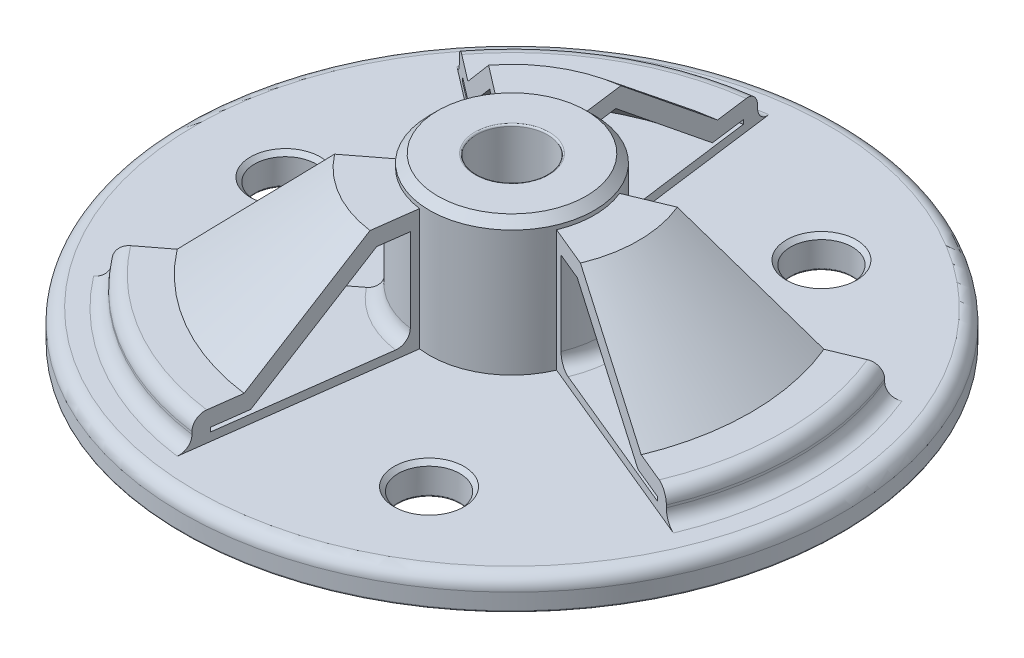
SolidWorks part; units mm, degrees
note: '?' marks a value the reader was unsure of.
material "ABS"
ref_plane "Front Plane" through (0, 0, 0) normal (0, 0, 1) x (1, 0, 0)
ref_plane "Top Plane" through (0, 0, 0) normal (0, 1, 0) x (1, 0, 0)
ref_plane "Right Plane" through (0, 0, 0) normal (1, 0, 0) x (0, 0, -1)
sketch "Sketch1" plane through (0, 0, 0) normal (0, 0, 1) x (1, 0, 0)
  line L0 (0, 0) -> (0, 25.4) construction
  line L1 (5.461, 25.4) -> (12.7, 25.4)
  line L2 (5.461, 0) -> (50.8, 0)
  line L3 (50.8, 0) -> (50.8, 4.7625)
  line L4 (50.8, 4.7625) -> (12.7, 4.7625)
  line L5 (12.7, 4.7625) -> (12.7, 25.4)
  line L6 (5.461, 25.4) -> (5.461, 0)
  dimension "D1" = 5.461
  dimension "D2" = 12.7
  dimension "D3" = 50.8
  dimension "D4" = 4.7625
  dimension "D5" = 25.4
revolve "Revolve1" add sketch "Sketch1" angle 360 about L0
hole_wizard "CBORE for #10 Socket Head Cap Screw1" positions "Sketch4" profile "Sketch6" counterbore size "#10" standard "ANSI Inch" end condition through all
sketch "Sketch4" plane through (0, 4.7625, 0) normal (0, 1, 0) x (1, 0, 0)
  line L4 (0, 0) -> (-34.925, 0) construction
  line L6 (0, 0) -> (17.4625, 30.2459) construction
  line L7 (0, 0) -> (17.4625, -30.2459) construction
  circle A1 centre (0, 0) radius 34.925 construction
  point P40 (-34.925, 0)
  point P43 (17.4625, -30.2459)
  point P46 (17.4625, 30.2459)
  dimension "D1" = 69.85
sketch "Sketch6" plane through (17.4625, 4.7625, -30.2459) normal (1, 0, 0) x (0, 0, 1)
  line L0 (0, 0) -> (0, 4.7625)
  line L1 (0, 4.7625) -> (2.8067, 4.7625)
  line L3 (2.8067, 4.7625) -> (2.8067, 4.826)
  line L4 (4.7625, 4.826) -> (2.8067, 4.826)
  line L5 (4.7625, 4.826) -> (4.7625, 0.635)
  line L6 (4.7625, 0.635) -> (5.3975, 0)
  line L7 (5.3975, 0) -> (0, 0)
  line L8 (-4.7625, 0.635) -> (-5.3975, 0) construction
  line L11 (0, -6.35) -> (0, 107.95) construction
  dimension "Thru Hole Dia." = 5.6134
  dimension "Thru Hole Depth" = 4.7625
  dimension "C'Bore Dia." = 9.525
  dimension "C'Bore Depth" = 4.826
  dimension "Near C'Sink Dia." = 10.795
  dimension "Near C'Sink Angle" = 90
sketch "Sketch7" plane through (0, 0, 0) normal (0, 0, 1) x (1, 0, 0)
  line L0 (12.7, 22.225) -> (19.05, 22.225)
  line L1 (12.7, 4.7625) -> (12.7, 25.4) construction
  line L2 (19.05, 22.225) -> (36.3504, 7.9375)
  line L3 (36.3504, 7.9375) -> (42.7004, 7.9375)
  line L4 (42.7004, 7.9375) -> (42.7004, 4.7625)
  line L5 (50.8, 4.7625) -> (-50.8, 4.7625) construction
  line L6 (12.7, 22.225) -> (12.7, 4.7625)
  line L7 (12.7, 4.7625) -> (42.7004, 4.7625)
  line L8 (0, 25.4) -> (0, 4.7625) construction
  line L9 (12.7, 25.4) -> (-12.7, 25.4) construction
  line L10 (12.7, 4.7625) -> (-12.7, 4.7625) construction
  dimension "D1" = 19.05
  dimension "D2" = 36.3504
  dimension "D3" = 3.175
  dimension "D4" = 6.35
  dimension "D5" = 3.175
revolve "Revolve-Thin1" add sketch "Sketch7" angle 45 mid plane about L8
ref_axis "Axis1" through (0, 25.4, 0) along (0, -1, 0)?
pattern_circular "CirPattern1" count 3 over 360 about axis through (0, 0, 0) along (0, 1, 0) of "Revolve-Thin1"
sketch "Sketch8" plane through (0, 0, 0) normal (0, -1, 0) x (1, 0, 0)
  circle A0 centre (0, 0) radius 7.9375
  circle A1 centre (0, 0) radius 5.461
  dimension "D1" = 15.875
extrude "Boss-Extrude1" add sketch "Sketch8" along normal blind 12.7 draft 1
fillet "Fillet1" radius 2.032 10 edges at (-21.9852, 4.7625, -38.0795) (-21.9852, 9.2075, -38.0795) (-6.985, 6.0325, -12.0984) (43.9704, 4.7625, 0) (43.9704, 9.2075, 0) (13.97, 6.0325, 0) (0, 4.7625, -50.8) (-21.9852, 4.7625, 38.0795) (-21.9852, 9.2075, 38.0795) (-6.985, 6.0325, 12.0984)
fillet "Fillet2" radius 0.254 8 edges at (0, 25.4, -5.461) (0, 0, -50.8) (-34.925, 0, -4.7625) (17.4625, 0, -35.0084) (17.4625, 0, 25.4834) (0, -12.7, -7.7158) (0, -12.7, -5.6827) (0, 0, -7.9375)
chamfer "Chamfer1" distance 1.27 angle 45 1 edges at (0, 25.4, -12.7)
